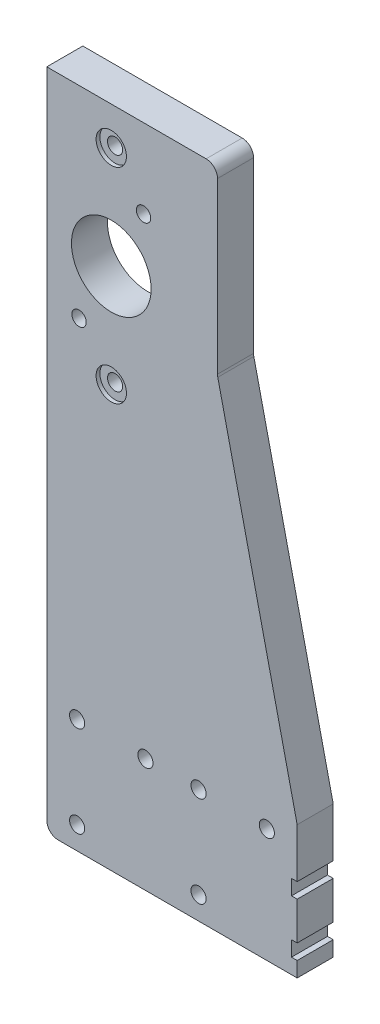
SolidWorks part; units mm, degrees
ref_plane "前视基准面" through (0, 0, 0) normal (0, 0, 1) x (1, 0, 0)
ref_plane "上视基准面" through (0, 0, 0) normal (0, 1, 0) x (1, 0, 0)
ref_plane "右视基准面" through (0, 0, 0) normal (1, 0, 0) x (0, 0, -1)
sketch "草图5" plane through (0, 0, 0) normal (0, 0, 1) x (1, 0, 0)
  line L0 (0, 0) -> (0, 175)
  line L1 (0, 175) -> (45, 175)
  line L2 (45, 175) -> (45, 127)
  line L3 (45, 127) -> (66, 35)
  line L4 (66, 35) -> (66, 0)
  line L5 (66, 0) -> (0, 0)
  line L6 (17, 175) -> (17, 0) construction
  dimension "D1" = 66
  dimension "D2" = 175
  dimension "D3" = 45
  dimension "D4" = 48
  dimension "D5" = 35
  dimension "D6" = 17
extrude "凸台-拉伸1" add sketch "草图5" along normal blind 9.5
sketch "草图6" plane through (0, 0, 9.5) normal (0, 0, 1) x (1, 0, 0)
  line L0 (17, 175) -> (17, 0) construction
  line L1 (45, 175) -> (0, 175) construction
  line L2 (0, 0) -> (66, 0) construction
  line L3 (0, 175) -> (0, 0) construction
  circle A0 centre (17, 165) radius 2
  circle A1 centre (17, 111) radius 2
  dimension "D2" = 4
  dimension "D3" = 10
  dimension "D4" = 54
  dimension "D1" = 17
extrude "切除-拉伸5" cut sketch "草图6" against normal through all contours A1 | A0
sketch "草图7" plane through (0, 0, 9.5) normal (0, 0, 1) x (1, 0, 0)
  circle A0 centre (17, 165) radius 4
  circle A1 centre (17, 111) radius 4
  dimension "D1" = 8
extrude "切除-拉伸6" cut sketch "草图7" against normal blind 1
fillet "圆角1" radius 3 3 edges at (0, 0, 4.75) (45, 127, 4.75) (45, 175, 4.75)
sketch "草图8" plane through (0, 0, 9.5) normal (0, 0, 1) x (1, 0, 0)
  line L0 (17, 165) -> (17, 111) construction
  circle A3 centre (17, 138) radius 10.5
  dimension "D1" = 21
extrude "切除-拉伸7" cut sketch "草图8" against normal blind 10
sketch "草图10" plane through (0, 0, 9.5) normal (0, 0, 1) x (1, 0, 0)
  circle A0 centre (25.5, 154.1497) radius 1.9
  circle A2 centre (8.5, 121.8503) radius 1.9
  dimension "D1" = 3.8
extrude "切除-拉伸8" cut sketch "草图10" against normal through all
sketch "草图12" plane through (66, 0, 0) normal (1, 0, 0) x (0, 0, -1)
  line L0 (0, 0) -> (0, 35) construction
  line L5 (-9.5, 0) -> (-9.5, 35) construction
  line L7 (0, 8) -> (-9.5, 8)
  line L8 (0, 8) -> (0, 4)
  line L9 (0, 4) -> (-9.5, 4)
  line L10 (-9.5, 8) -> (-9.5, 4)
  line L15 (-9.5, 22) -> (0, 22)
  line L16 (-9.5, 22) -> (-9.5, 18)
  line L17 (-9.5, 18) -> (0, 18)
  line L18 (0, 22) -> (0, 18)
extrude "切除-拉伸10" cut sketch "草图12" against normal blind 1.5
sketch "草图15" plane through (0, 0, 9.5) normal (0, 0, 1) x (1, 0, 0)
  circle A0 centre (58, 30.03) radius 2
  circle A1 centre (40, 30.03) radius 2
  circle A2 centre (26, 30.03) radius 2
  circle A3 centre (8, 30.03) radius 2
  circle A4 centre (40, 6.03) radius 2
  circle A5 centre (8, 6.03) radius 2
  dimension "D1" = 4
extrude "切除-拉伸13" cut sketch "草图15" against normal through all
sketch "草图16" plane through (0, 0, 0) normal (0, 0, -1) x (-1, 0, 0)
  circle A0 centre (-58, 30.03) radius 4
  circle A1 centre (-40, 30.03) radius 4
  circle A2 centre (-26, 30.03) radius 4
  circle A3 centre (-8, 30.03) radius 4
  circle A4 centre (-40, 6.03) radius 4
  circle A5 centre (-8, 6.03) radius 4
  dimension "D1" = 8
extrude "切除-拉伸14" cut sketch "草图16" against normal blind 4
sketch "草图18" plane through (0, 0, 0) normal (0, 0, -1) x (-1, 0, 0)
  circle A0 centre (-17, 111) radius 4
  circle A1 centre (-17, 165) radius 4
  dimension "D1" = 8
extrude "切除-拉伸15" cut sketch "草图18" against normal blind 4
